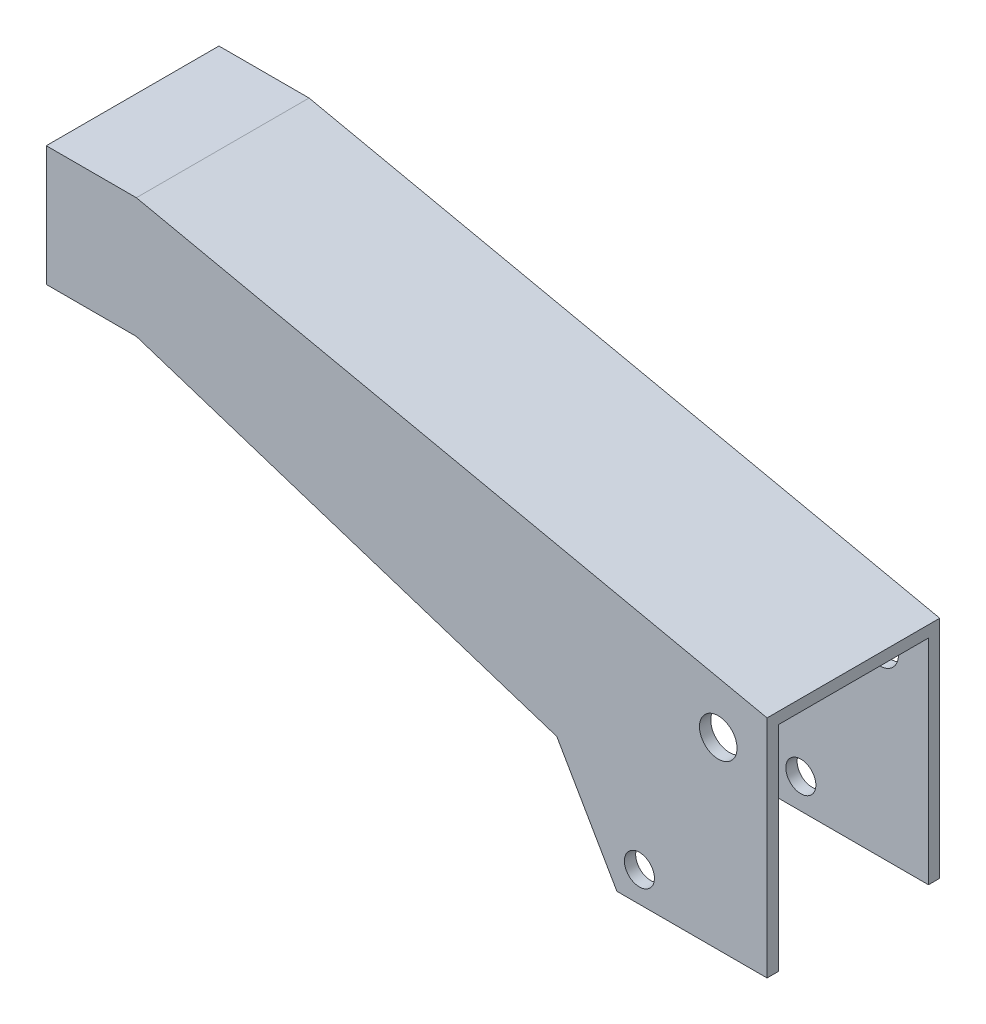
SolidWorks part; units mm, degrees
ref_plane "Front Plane" through (0, 0, 0) normal (0, 0, 1) x (1, 0, 0)
ref_plane "Top Plane" through (0, 0, 0) normal (0, 1, 0) x (1, 0, 0)
ref_plane "Right Plane" through (0, 0, 0) normal (1, 0, 0) x (0, 0, -1)
sketch "Sketch1" plane through (0, 0, 0) normal (0, 0, 1) x (1, 0, 0)
  line L0 (-609.6, 304.8) -> (-533.4, 304.8)
  line L1 (-609.6, 304.8) -> (-609.6, 203.2)
  line L2 (-609.6, 203.2) -> (-533.4, 203.2)
  line L3 (-177.8, 87.9882) -> (-127, 0)
  line L4 (-127, 0) -> (0, 0)
  line L5 (0, 0) -> (0, 190.5)
  line L6 (0, 190.5) -> (-533.4, 304.8)
  line L7 (-533.4, 203.2) -> (-177.8, 87.9882)
  point P6 (0, 0)
  point P8 (-511.0303, 203.2)
  point P9 (0, 0)
  point P10 (-176.322, 88.8251)
  point P11 (-533.4, 304.8)
  point P12 (0, 193.2599)
  dimension "D1" = 76.2
  dimension "D2" = 101.6
  dimension "D3" = 609.6
  dimension "D4" = 127
  dimension "D5" = 101.6
  dimension "D6" = 203.2
  dimension "D7" = 190.5
  dimension "D8" = 120
extrude "Boss-Extrude1" add sketch "Sketch1" against normal blind 9.525
ref_plane "Plane1" through (0, 0, 127) normal (0, 0, 1) x (1, 0, 0)
sketch "Sketch2" plane through (0, 0, 127) normal (0, 0, 1) x (1, 0, 0)
  line L8 (-533.4, 203.2) -> (-177.8, 87.9882)
  line L9 (-177.8, 87.9882) -> (-127, 0)
  line L10 (-127, 0) -> (0, 0)
  line L11 (0, 0) -> (0, 190.5)
  line L12 (0, 190.5) -> (-533.4, 304.8)
  line L13 (-533.4, 304.8) -> (-609.6, 304.8)
  line L14 (-609.6, 304.8) -> (-609.6, 203.2)
  line L15 (-609.6, 203.2) -> (-533.4, 203.2)
  line L16 (-533.4, 203.2) -> (-177.8, 87.9882)
  line L17 (-177.8, 87.9882) -> (-127, 0)
  line L18 (-127, 0) -> (0, 0)
  line L19 (0, 0) -> (0, 190.5)
  line L20 (0, 190.5) -> (-533.4, 304.8)
  line L21 (-533.4, 304.8) -> (-609.6, 304.8)
  line L22 (-609.6, 304.8) -> (-609.6, 203.2)
  line L23 (-609.6, 203.2) -> (-533.4, 203.2)
  dimension "D1" = 0
extrude "Boss-Extrude2" add sketch "Sketch2" along normal blind 9.525 separate body
sketch "Sketch3" plane through (0, 0, 136.525) normal (0, 0, 1) x (1, 0, 0)
  line L6 (-609.6, 295.275) -> (-609.6, 304.8)
  line L7 (-609.6, 304.8) -> (-533.4, 304.8)
  line L8 (-533.4, 304.8) -> (0, 190.5)
  line L9 (-9.525, 0) -> (-9.525, 182.7998)
  line L10 (-9.525, 182.7998) -> (-534.4091, 295.275)
  line L11 (-534.4091, 295.275) -> (-609.6, 295.275)
  line L12 (-9.525, 182.7998) -> (0, 180.7588)
  line L13 (-9.525, 182.7998) -> (-534.4091, 295.275)
  line L14 (-534.4091, 295.275) -> (-609.6, 295.275)
  line L15 (0, 0) -> (0, 190.5) construction
  line L16 (0, 180.7588) -> (0, 190.5)
  dimension "D1" = 9.525
extrude "Boss-Extrude3" add sketch "Sketch3" against normal up to surface (136.525 mm away) up to face at (-323.85, 161.811, 0)
sketch "Sketch5" plane through (0, 0, 136.525) normal (0, 0, 1) x (1, 0, 0)
  line L2 (-127, 0) -> (0, 0) construction
  line L3 (0, 0) -> (0, 190.5) construction
  circle A0 centre (-41.275, 155.575) radius 15.875
  circle A1 centre (-107.95, 25.4) radius 12.7
  point P2 (-25.4, 155.575)
  point P5 (-41.275, 171.45)
  point P9 (-107.95, 12.7)
  point P10 (-120.65, 25.4)
  dimension "D1" = 25.4
  dimension "D3" = 31.75
  dimension "D6" = 25.4
  dimension "D2" = 19.05
  dimension "D4" = 12.7
  dimension "D5" = 6.35
extrude "Cut-Extrude1" cut sketch "Sketch5" against normal through all
